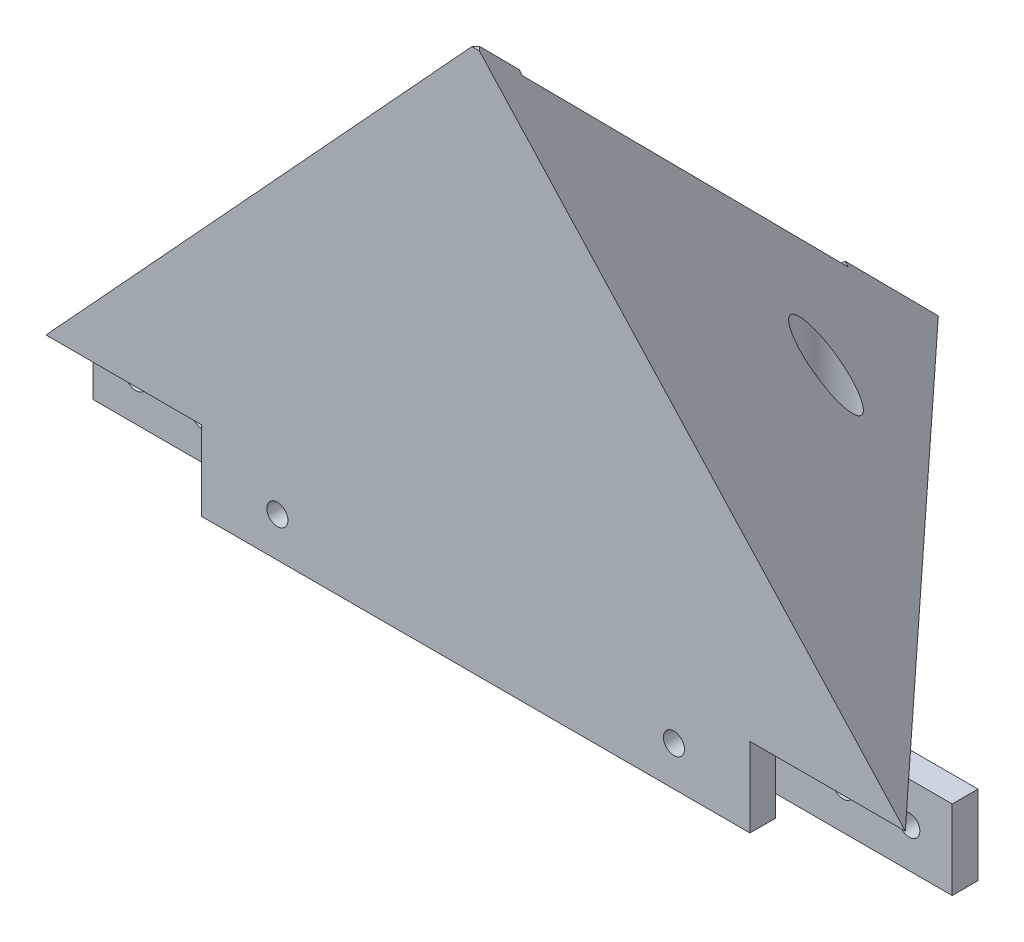
SolidWorks part; units mm, degrees
ref_plane "Front Plane" through (0, 0, 0) normal (0, 0, 1) x (1, 0, 0)
ref_plane "Top Plane" through (0, 0, 0) normal (0, 1, 0) x (1, 0, 0)
ref_plane "Right Plane" through (0, 0, 0) normal (1, 0, 0) x (0, 0, -1)
sketch "Sketch1" plane through (0, 0, 0) normal (0, 1, 0) x (1, 0, 0)
  line L0 (0, -70) -> (65, 0)
  line L1 (0, 0) -> (130, 0)
  line L2 (0, 0) -> (0, -70)
  line L3 (0, -70) -> (130, -70)
  line L4 (130, 0) -> (130, -70)
  line L5 (65, 0) -> (130, -70)
  dimension "D1" = 70
  dimension "D2" = 130
extrude "Boss-Extrude1" add sketch "Sketch1" along normal blind 70 contours L5 L0 L3 region at (65, 0, 46.6667)
draft "Draft3" type of draft neutral plane draft angle 34 faces to draft 2 face at (97.5, 35, 35) face at (32.5, 35, 35) neutral plane through (0, 0, 0) neutral plane normal (0, -1, 0) reverse direction yes parameters "D1"=34
sketch "Sketch2" plane through (0, 0, 0) normal (0, -1, 0) x (1, 0, 0)
  line L0 (65, 0) -> (65, 82.5082) construction
  line L1 (0, 70) -> (130, 70) construction
  circle A0 centre (51, 31) radius 4
  circle A1 centre (79, 31) radius 4
  dimension "D1" = 14
  dimension "D2" = 8
  dimension "D3" = 39
extrude "Cut-Extrude1" cut sketch "Sketch2" against normal blind 70
sketch "Sketch5" plane through (0, 0, 0) normal (1, 0, 0) x (0, 0, -1)
  line L0 (-70, 0) -> (-70, 75.6378) construction
  line L1 (-14.08, 14.204) -> (-63.3599, 63.9181)
  line L2 (-69.3887, 70) -> (0, 0) construction
  line L3 (-63.3599, 63.9181) -> (-66.3974, 52.7778)
  line L4 (-66.3974, 52.7778) -> (-17.1174, 3.0637)
  line L5 (-14.08, 14.204) -> (-17.1174, 3.0637)
  dimension "D1" = 70
  dimension "D2" = 20
  dimension "D3" = 60
  dimension "D4" = 70
  dimension "D5" = 10
extrude "Cut-Extrude3" cut sketch "Sketch5" along normal blind 1 from offset 64.5
sketch "Sketch6" plane through (0, 0, 0) normal (0, -1, 0) x (1, 0, 0)
  line L0 (0, 70) -> (130, 70)
  line L1 (0, 70) -> (0, 59)
  line L2 (130, 70) -> (130, 59)
  line L3 (0, 59) -> (130, 59)
  line L4 (0, 66.1) -> (130, 66.1)
  line L5 (0, 64.5) -> (130, 64.5) construction
  line L6 (0, 62.9) -> (130, 62.9)
  line M9 (65, 0) -> (130, 70)
  line M10 (130, 70) -> (0, 70)
  line M11 (0, 70) -> (65, 0)
  dimension "D1" = 11
  dimension "D2" = 3.9
extrude "Boss-Extrude2" add sketch "Sketch6" along normal blind 12 contours L4 M11 M9 M10 | L6 L3 M11 M9 | L6 L1 L3 M11 | L1 L4 M11 | L4 L2 M9 | L6 L3 L2 M9 region at (1.2071, 0, 67.4) region at (65, 0, 68.0686) region at (128.7929, 0, 67.4) region at (4.2668, 0, 60.8099) region at (65, 0, 60.9708) region at (125.7332, 0, 60.8099)
sketch "Sketch7" plane through (0, 0, 59) normal (0, 0, -1) x (-1, 0, 0)
  line L0 (-65, 0) -> (-65, -12) construction
  line L1 (-10.2143, 0) -> (-119.7857, 0) construction
  line L2 (0, -12) -> (-130, -12) construction
  line L3 (-130, -12) -> (-130, 0) construction
  line L5 (-106.5, 0) -> (-106.5, -12)
  line L6 (-65, 0) -> (-119.7857, 0) construction
  line L7 (-23.5, 0) -> (-23.5, -12)
  line L8 (-106.5, 0) -> (-130, 0)
  line L9 (-130, 0) -> (-130, -12)
  line L10 (-130, -12) -> (-106.5, -12)
  line L11 (0, 0) -> (0, -12)
  line L12 (-23.5, 0) -> (0, 0)
  line L13 (-23.5, 0) -> (-23.5, -12)
  line L14 (0, -12) -> (-23.5, -12)
  circle A0 centre (-95, -6) radius 1.6
  circle A1 centre (-123.5, -6) radius 1.6
  circle A2 centre (-113.5, -6) radius 1.6
  circle A3 centre (-6.5, -6) radius 1.6
  circle A4 centre (-16.5, -6) radius 1.6
  circle A5 centre (-35, -6) radius 1.6
  line M1 (0, 0) -> (-10.2143, 0)
  line M2 (-10.2143, 0) -> (-119.7857, 0)
  line M3 (-119.7857, 0) -> (-130, 0)
  line M4 (-130, 0) -> (-130, -12)
  line M5 (-130, -12) -> (0, -12)
  line M6 (0, -12) -> (0, 0)
  dimension "D1" = 6
  dimension "D2" = 35
  dimension "D3" = 3.2
  dimension "D4" = 3.2
  dimension "D5" = 3.2
  dimension "D9" = 6
  dimension "D6" = 10
  dimension "D7" = 6.5
  dimension "D8" = 18.5
  dimension "D10" = 7
extrude "Cut-Extrude4" cut sketch "Sketch7" against normal blind 70 contours A2 | A1 | A0 | A5 | A4 | A3
extrude "Cut-Extrude5" cut sketch "Sketch7<3>" against normal blind 70 from offset 6 contours L5 A2 A1 M2 M3 M4 M5 | L7 A3 A4 M2 M5 M6 M1 region at (118.2349, -6, 59) region at (11.7651, -6, 59) offset against normal yes
sketch "Sketch7<3>" plane through (0, 0, 59) normal (0, 0, -1) x (-1, 0, 0) same geometry as "Sketch7"
